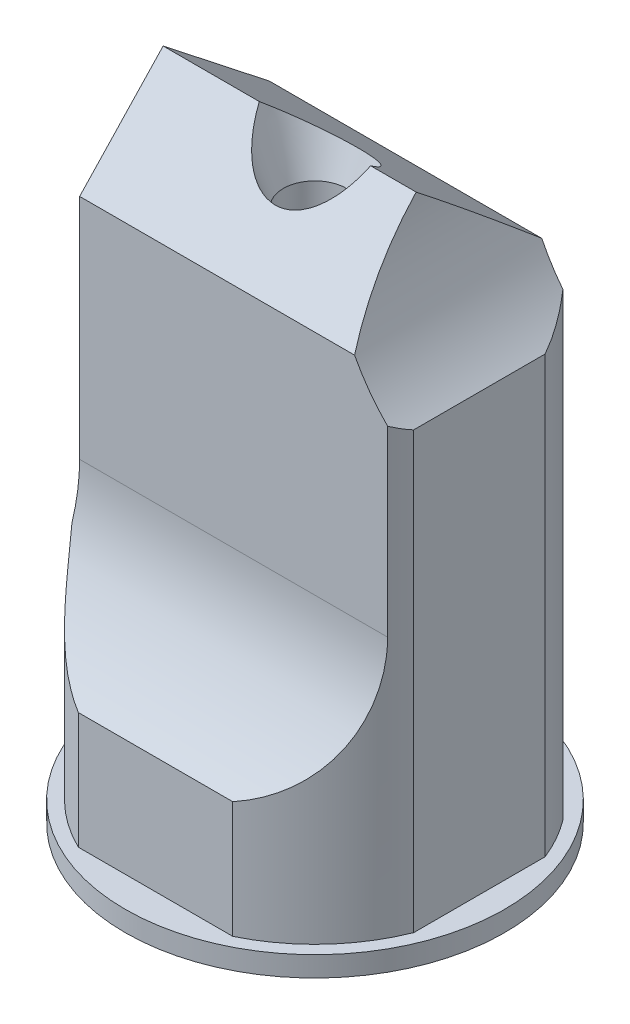
SolidWorks part; units mm, degrees
ref_plane "Plano frontal" through (0, 0, 0) normal (0, 0, 1) x (1, 0, 0)
ref_plane "Plano superior" through (0, 0, 0) normal (0, 1, 0) x (1, 0, 0)
ref_plane "Plano direito" through (0, 0, 0) normal (1, 0, 0) x (0, 0, -1)
sketch "Esboço1" plane through (0, 0, 0) normal (0, 1, 0) x (1, 0, 0)
  circle A0 centre (0, 0) radius 7.5
  circle A1 centre (0, 0) radius 1.25
  dimension "D1" = 15
  dimension "D2" = 2.5
extrude "Ressalto-extrusão1" add sketch "Esboço1" along normal blind 23.6
sketch "Esboço2" plane through (0, 23.6, 0) normal (0, 1, 0) x (1, 0, 0)
  line L0 (6.5, -2.5981) -> (6.5, 2.5981)
  line L2 (-3.0512, -6.3) -> (3.0512, -6.3)
  line L3 (-6, 4.2) -> (-6, -3.6056)
  line L4 (-6, 4.2) -> (5.6, 4.2)
  line L5 (6.5, 0) -> (0, 0) construction
  line L6 (0, 0) -> (0, -6.3) construction
  arc A0 (6.5, 2.5981) -> (5.6, 4.2) centre (0, 0) ccw
  arc A1 (3.0512, -6.3) -> (6.5, -2.5981) centre (0, 0) ccw
  arc A2 (-6, -3.6056) -> (-3.0512, -6.3) centre (0, 0) ccw
  circle A3 centre (0, 0) radius 7.5
  circle A5 centre (0, 0) radius 7.5 construction
  circle M12 centre (0, 0) radius 7.5
  dimension "D5" = 7
  dimension "D1" = 4.2
  dimension "D2" = 6.3
  dimension "D3" = 7.8056
  dimension "D4" = 6
  dimension "D6" = 6.5
  dimension "D7" = 5.1962
  dimension "D8" = 6.1025
extrude "Corte-extrusão1" cut sketch "Esboço2" against normal offset from surface (22.8 mm away) 0.8 contours A2 L3 L4 A0 L0 A1 L2 M12 region at (-7.2879, 23.6, 0) up to face at (0, 0, 7.5)
sketch "Esboço3" plane through (6.5, 0, 0) normal (1, 0, 0) x (0, 0, -1)
  line L8 (-6.3, 0.8) -> (-6.3, 5.41)
  line L9 (7.5, 0.8) -> (-7.5, 0.8) construction
  line L10 (-6.3, 0.8) -> (-6.3, 23.6) construction
  line L11 (-3.3, 11.1021) -> (-3.3, 20.1021)
  line L12 (-3.3, 20.1021) -> (0, 23.6)
  line L13 (-2.5981, 23.6) -> (2.5981, 23.6) construction
  line L14 (0, 0) -> (0, 23.6) construction
  line L15 (0, 23.6) -> (4.2, 20.3)
  line L16 (4.2, 0.8) -> (4.2, 23.6) construction
  line L18 (-6.3, 0.8) -> (-7.5, 0.8)
  line L19 (-7.5, 0.8) -> (-7.5, 26.4981)
  line L20 (-7.5, 26.4981) -> (4.2, 26.4981)
  line L21 (4.2, 26.4981) -> (4.2, 20.3)
  arc A1 (-6.3, 5.41) -> (-3.3, 11.1021) centre (-10.2, 11.1021) ccw
  dimension "D3" = 13.8
  dimension "D2" = 4.61
  dimension "D4" = 3.9
  dimension "D5" = 9
  dimension "D6" = 3.3
extrude "Corte-extrusão2" cut sketch "Esboço3" against normal through all
sketch "Esboço4" plane through (0, 0, 0) normal (0, -1, 0) x (1, 0, 0)
  circle A0 centre (0, 0) radius 3.5
  circle A1 centre (0, 0) radius 2.5
  circle M4 centre (0, 0) radius 1.25
  dimension "D1" = 7
  dimension "D2" = 5
extrude "Corte-extrusão3" cut sketch "Esboço4" against normal blind 4 contours A0 A1 | A1 M4 region at (-3.401, 0, 0) region at (-2.4293, 0, 0)
extrude "Corte-extrusão4" cut sketch "Esboço4<3>" against normal blind 20 contours A1 M4 region at (-2.4293, 0, 0)
sketch "Esboço4<3>" plane through (0, 0, 0) normal (0, -1, 0) x (1, 0, 0) same geometry as "Esboço4"
ref_plane "Plano1" through (0, 23.6, 0) normal (0, 1, 0) x (1, 0, 0)
sketch "Esboço5" plane through (0, 23.6, 0) normal (0, 1, 0) x (1, 0, 0)
  circle A0 centre (0, 0) radius 2.2
  dimension "D1" = 4.4
ref_plane "Plano2" through (0, 21.1, 0) normal (0, -1, 0) x (-1, 0, 0)
sketch "Esboço6" plane through (0, 21.1, 0) normal (0, -1, 0) x (-1, 0, 0)
  circle A0 centre (0, 0) radius 1.25
  dimension "D1" = 2.5
loft "Loft de corte1" cut profiles "Esboço5", "Esboço6" connector at (0.5805, 23.6, 2.122) connector at (0.1481, 21.1, 1.2412)
sketch "Esboço7" plane through (0, 0, 3.3) normal (0, 0, 1) x (1, 0, 0)
  line L0 (6.5, 23.6) -> (4, 23.6) construction
  line L1 (2.2, 23.6) -> (6.5, 23.6) construction
  line L2 (4, 23.6) -> (4, 16.9594) construction
  circle A0 centre (11.5, 23.6) radius 7.5
  dimension "D1" = 2.5
  dimension "D2" = 15
extrude "Corte-extrusão5" cut sketch "Esboço7" against normal through all
chamfer "Chanfro1" distance 2 angle 45 1 edges at (0, 4, -2.5)
